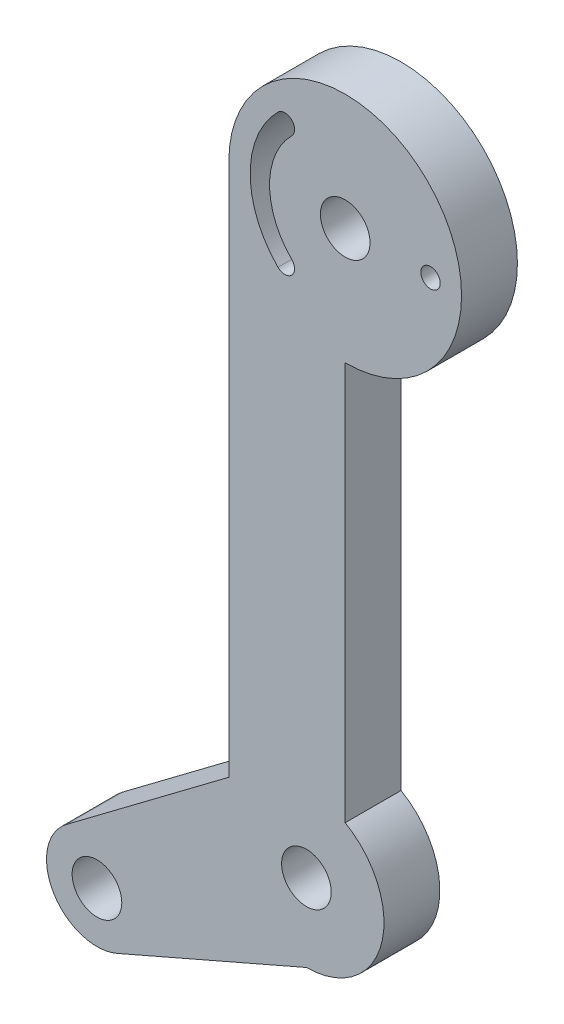
SolidWorks part; units mm, degrees
ref_plane "Front Plane" through (0, 0, 0) normal (0, 0, 1) x (1, 0, 0)
ref_plane "Top Plane" through (0, 0, 0) normal (0, 1, 0) x (1, 0, 0)
ref_plane "Right Plane" through (0, 0, 0) normal (1, 0, 0) x (0, 0, -1)
sketch "Sketch1" plane through (0, 0, 0) normal (0, 0, 1) x (1, 0, 0)
  line L0 (-5, 37.5) -> (-5, 3.1174)
  line L1 (2.5, 30) -> (2.5, 4.3301)
  line L2 (-12.2021, -10.3152) -> (0, -5)
  line L3 (-15.4525, -4.7374) -> (-5, 3.1174)
  circle A0 centre (0, 0) radius 1.6
  arc A1 (0, -5) -> (2.5, 4.3301) centre (0, 0) ccw
  circle A2 centre (-13.5, -7.3356) radius 1.6
  arc A3 (-15.4525, -4.7374) -> (-12.2021, -10.3152) centre (-13.5, -7.3356) ccw
  circle A4 centre (2.5, 37.5) radius 1.6
  arc A5 (2.5, 30) -> (-5, 37.5) centre (2.5, 37.5) ccw
  point P13 (0, 0)
  dimension "D1" = 3.2
  dimension "D4" = 5
  dimension "D5" = 3.25
  dimension "D6" = 7.5
  dimension "D7" = 12.2021
  dimension "D8" = 13.5
  dimension "D9" = 15.4525
  dimension "D10" = 30
extrude "Boss-Extrude1" add sketch "Sketch1" along normal blind 3.6
sketch "Sketch2" plane through (0, 0, 3.6) normal (0, 0, 1) x (1, 0, 0)
  line L0 (2.5, 37.5) -> (-1.3891, 33.6109) construction
  line L1 (2.5, 37.5) -> (-1.3891, 41.3891) construction
  line L3 (2.5, 37.5) -> (8, 37.5) construction
  arc A0 (-1.3891, 33.6109) -> (-1.3891, 41.3891) centre (2.5, 37.5) cw construction
  arc A1 (-0.9471, 40.9471) -> (-1.831, 41.831) centre (-1.3891, 41.3891) ccw
  arc A2 (-1.831, 33.169) -> (-0.9471, 34.0529) centre (-1.3891, 33.6109) ccw
  arc A3 (-1.831, 33.169) -> (-1.831, 41.831) centre (2.5, 37.5) cw
  arc A4 (-0.9471, 34.0529) -> (-0.9471, 40.9471) centre (2.5, 37.5) cw
  circle A5 centre (8, 37.5) radius 0.625
  dimension "D3" = 1.25
  dimension "D1" = 5.5
extrude "Cut-Extrude1" cut sketch "Sketch2" against normal through all
